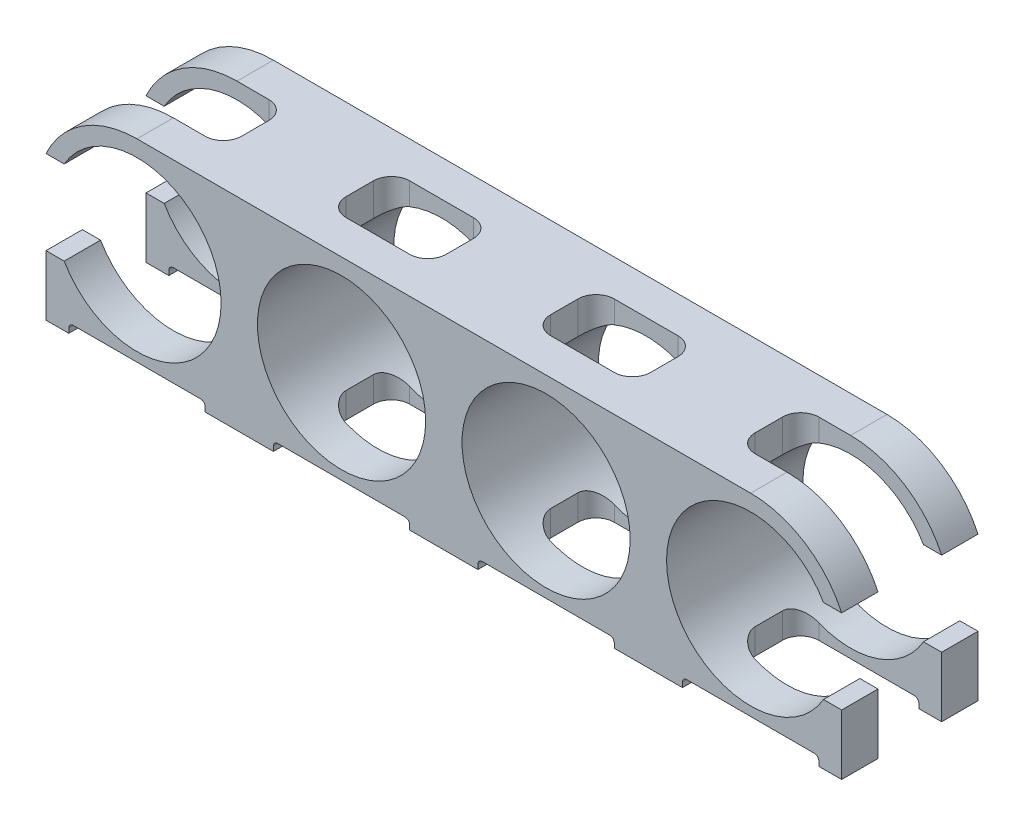
SolidWorks part; units mm, degrees
ref_plane "Front Plane" through (0, 0, 0) normal (0, 0, 1) x (1, 0, 0)
ref_plane "Top Plane" through (0, 0, 0) normal (0, 1, 0) x (1, 0, 0)
ref_plane "Right Plane" through (0, 0, 0) normal (1, 0, 0) x (0, 0, -1)
sketch "Sketch1" plane through (0, 0, 0) normal (0, 0, 1) x (1, 0, 0)
  line L0 (-41.7607, -4.625) -> (-43.7607, -4.625)
  line L1 (-41.7607, 4.625) -> (-43.7607, 4.625)
  line L2 (-33.75, 11.0275) -> (33.75, 11.0275)
  line L3 (-43.7607, -11.25) -> (43.7607, -11.25)
  line L4 (41.7607, 4.625) -> (43.7607, 4.625)
  line L5 (41.7607, -4.625) -> (43.7607, -4.625)
  line L7 (-43.7607, -11.25) -> (-43.7607, -4.625)
  line L8 (43.7607, -4.625) -> (43.7607, -11.25)
  circle A0 centre (-11.25, 0) radius 9.25 construction
  circle A1 centre (11.25, 0) radius 9.25 construction
  circle A2 centre (-33.75, 0) radius 9.25 construction
  circle A3 centre (33.75, 0) radius 9.25 construction
  arc A4 (-41.7607, 4.625) -> (-33.75, 9.25) centre (-33.75, 0) cw
  arc A5 (-43.7607, 4.625) -> (-33.75, 11.0275) centre (-33.75, 0) cw
  arc A6 (-33.75, 9.25) -> (-33.75, -9.25) centre (-33.75, 0) cw
  arc A7 (-33.75, -9.25) -> (-41.7607, -4.625) centre (-33.75, 0) cw
  circle A9 centre (-11.25, 0) radius 9.25
  circle A10 centre (11.25, 0) radius 9.25
  arc A12 (33.75, 11.0275) -> (43.7607, 4.625) centre (33.75, 0) cw
  arc A14 (33.75, 9.25) -> (41.7607, 4.625) centre (33.75, 0) cw
  arc A15 (41.7607, -4.625) -> (33.75, -9.25) centre (33.75, 0) cw
  arc A16 (33.75, 9.25) -> (33.75, -9.25) centre (33.75, 0) ccw
  point P30 (-43.7607, -7.9375)
  dimension "D5" = 18.5
  dimension "D6" = 60
  dimension "D8" = 2
  dimension "D1" = 22.5
  dimension "D2" = 11.25
  dimension "D3" = 22.5
  dimension "D4" = 22.5
  dimension "D7" = 2
extrude "Boss-Extrude1" add sketch "Sketch1" along normal blind 15
sketch "Sketch2" plane through (0, 11.0275, 0) normal (0, 1, 0) x (1, 0, 0)
  line L0 (0, 0) -> (0, -15) construction
  line L17 (30.25, -4) -> (46.25, -4)
  line L18 (-30.25, -9) -> (-46.25, -6) construction
  line L23 (-30.25, -6) -> (-46.25, -9) construction
  line L24 (-7.75, -9) -> (-14.75, -6) construction
  line L25 (33.75, -15) -> (-33.75, -15) construction
  line L27 (-7.75, -6) -> (-14.75, -9) construction
  line L33 (-48.25, -6) -> (-48.25, -9)
  line L34 (-30.25, -11) -> (-46.25, -11)
  line L35 (7.75, -4) -> (14.75, -4)
  line L36 (5.75, -6) -> (5.75, -9)
  line L37 (7.75, -11) -> (14.75, -11)
  line L38 (16.75, -6) -> (16.75, -9)
  line L39 (7.75, -6) -> (14.75, -9) construction
  line L40 (7.75, -9) -> (14.75, -6) construction
  line L41 (-28.25, -6) -> (-28.25, -9)
  line L42 (28.25, -6) -> (28.25, -9)
  line L43 (30.25, -11) -> (46.25, -11)
  line L44 (48.25, -6) -> (48.25, -9)
  line L45 (30.25, -6) -> (46.25, -9) construction
  line L46 (30.25, -9) -> (46.25, -6) construction
  line L47 (-16.75, -6) -> (-16.75, -9)
  line L48 (-7.75, -11) -> (-14.75, -11)
  line L49 (-5.75, -6) -> (-5.75, -9)
  line L50 (-7.75, -4) -> (-14.75, -4)
  line L51 (-30.25, -4) -> (-46.25, -4)
  arc A4 (16.75, -6) -> (14.75, -4) centre (14.75, -6) ccw
  arc A5 (7.75, -4) -> (5.75, -6) centre (7.75, -6) ccw
  arc A6 (5.75, -9) -> (7.75, -11) centre (7.75, -9) ccw
  arc A7 (14.75, -11) -> (16.75, -9) centre (14.75, -9) ccw
  arc A8 (48.25, -6) -> (46.25, -4) centre (46.25, -6) ccw
  arc A9 (30.25, -4) -> (28.25, -6) centre (30.25, -6) ccw
  arc A10 (28.25, -9) -> (30.25, -11) centre (30.25, -9) ccw
  arc A11 (46.25, -11) -> (48.25, -9) centre (46.25, -9) ccw
  arc A12 (-46.25, -11) -> (-48.25, -9) centre (-46.25, -9) cw
  arc A13 (-28.25, -9) -> (-30.25, -11) centre (-30.25, -9) cw
  arc A14 (-30.25, -4) -> (-28.25, -6) centre (-30.25, -6) cw
  arc A15 (-48.25, -6) -> (-46.25, -4) centre (-46.25, -6) cw
  arc A16 (-14.75, -11) -> (-16.75, -9) centre (-14.75, -9) cw
  arc A17 (-5.75, -9) -> (-7.75, -11) centre (-7.75, -9) cw
  arc A18 (-7.75, -4) -> (-5.75, -6) centre (-7.75, -6) cw
  arc A19 (-16.75, -6) -> (-14.75, -4) centre (-14.75, -6) cw
  point P0 (11.25, -7.5)
  point P6 (38.25, -7.5)
  point P20 (0, -7.5)
  dimension "D10" = 2
  dimension "D17" = 2
  dimension "D12" = 7
  dimension "D13" = 11
  dimension "D14" = 11.25
  dimension "D19" = 20
  dimension "D20" = 11.5
  dimension "D21" = 7
  dimension "D8" = 90
  dimension "D9" = 90
  dimension "D11" = 90
  dimension "D15" = 90
  dimension "D16" = 90
  dimension "D18" = 90
extrude "Cut-Extrude1" cut sketch "Sketch2" against normal up to surface (22.2775 mm away) up to face at (0, -11.25, 7.5)
sketch "Sketch3" plane through (0, -11.25, 0) normal (0, -1, 0) x (1, 0, 0)
  line L0 (0, 15) -> (0, 0) construction
  line L1 (-43.7607, 15) -> (43.7607, 15) construction
  line L2 (-43.7607, 0) -> (43.7607, 0) construction
  line L3 (-28.25, 7.5) -> (-16.75, 7.5) construction
  line L4 (-28.25, 6) -> (-28.25, 9) construction
  line L5 (-16.75, 9) -> (-16.75, 6) construction
  line L6 (16.75, 7.5) -> (28.25, 7.5) construction
  line L7 (16.75, 6) -> (16.75, 9) construction
  line L8 (28.25, 9) -> (28.25, 6) construction
  circle A0 centre (0, 7.5) radius 1.325
  circle A1 centre (-22.5, 7.5) radius 1.325
  circle A2 centre (22.5, 7.5) radius 1.325
  point P13 (0, 7.5)
  point P20 (-22.5, 7.5)
  point P21 (22.5, 7.5)
  dimension "D1" = 2.65
extrude "Cut-Extrude2" cut sketch "Sketch3" against normal blind 7
thread "Thread1" pitch 0.5 method cut profile "Thread Profile1" start angle 0, offset 0, length 0, pitch 0.5, diameter 2.65
ref_plane "Plane1" through (-21.175, -11.25, 7.5) normal (0, 0, 1) x (1, 0, 0)
sketch "Thread Profile1" plane through (-21.175, -11.25, 7.5) normal (0, 0, 1) x (1, 0, 0)
  line L0 (0, 0) -> (0, 0.5) construction
  line L1 (0, 0) -> (0.2706, 0.1562)
  line L2 (0.2706, 0.1562) -> (0.2706, 0.2187)
  line L3 (0.2706, 0.2187) -> (0, 0.375)
  line L4 (0.2706, 0.1875) -> (0, 0.1875) construction
  line L11 (0, 0) -> (0, 0.375)
  point P2 (0, 0)
  dimension "Pitch" = 0.5
  dimension "Profile_Angle" = 60
  dimension "Profile_Land" = 0.0625
  dimension "Profile_Height" = 0.2706
thread "Thread2" pitch 0.5 method cut profile "Thread Profile2" start angle 0, offset 0, length 0, pitch 0.5, diameter 2.65
ref_plane "Plane2" through (1.325, -11.25, 7.5) normal (0, 0, 1) x (1, 0, 0)
sketch "Thread Profile2" plane through (1.325, -11.25, 7.5) normal (0, 0, 1) x (1, 0, 0)
  line L0 (0, 0) -> (0, 0.5) construction
  line L1 (0, 0) -> (0.2706, 0.1562)
  line L2 (0.2706, 0.1562) -> (0.2706, 0.2187)
  line L3 (0.2706, 0.2187) -> (0, 0.375)
  line L4 (0.2706, 0.1875) -> (0, 0.1875) construction
  line L11 (0, 0) -> (0, 0.375)
  point P2 (0, 0)
  dimension "Pitch" = 0.5
  dimension "Profile_Angle" = 60
  dimension "Profile_Land" = 0.0625
  dimension "Profile_Height" = 0.2706
thread "Thread3" pitch 0.5 method cut profile "Thread Profile3" start angle 0, offset 0, length 0, pitch 0.5, diameter 2.65
ref_plane "Plane3" through (23.825, -11.25, 7.5) normal (0, 0, 1) x (1, 0, 0)
sketch "Thread Profile3" plane through (23.825, -11.25, 7.5) normal (0, 0, 1) x (1, 0, 0)
  line L0 (0, 0) -> (0, 0.5) construction
  line L1 (0, 0) -> (0.2706, 0.1562)
  line L2 (0.2706, 0.1562) -> (0.2706, 0.2187)
  line L3 (0.2706, 0.2187) -> (0, 0.375)
  line L4 (0.2706, 0.1875) -> (0, 0.1875) construction
  line L11 (0, 0) -> (0, 0.375)
  point P2 (0, 0)
  dimension "Pitch" = 0.5
  dimension "Profile_Angle" = 60
  dimension "Profile_Land" = 0.0625
  dimension "Profile_Height" = 0.2706
sketch "Sketch4" plane through (0, 0, 15) normal (0, 0, 1) x (1, 0, 0)
  line L0 (-20.5, 0) -> (-2, 0) construction
  line L1 (-43.7607, -11.25) -> (43.7607, -11.25) construction
  line L2 (-18.25, -10.25) -> (-4.25, -10.25)
  line L3 (-18.75, -10.75) -> (-18.75, -11.25)
  line L4 (-18.75, -11.25) -> (-3.75, -11.25)
  line L5 (-3.75, -10.75) -> (-3.75, -11.25)
  line L6 (-18.75, -10.25) -> (-3.75, -11.25) construction
  line L7 (-18.75, -11.25) -> (-3.75, -10.25) construction
  line L8 (0, 11.0275) -> (0, -11.25) construction
  line L9 (33.75, 11.0275) -> (-33.75, 11.0275) construction
  line L10 (-20.5, 0) -> (-24.5, 0) construction
  line L11 (-22.5, 11.0275) -> (-22.5, 0) construction
  line L12 (-26.25, -11.25) -> (-41.25, -10.25) construction
  line L13 (-26.25, -10.25) -> (-41.25, -11.25) construction
  line L14 (-41.25, -10.75) -> (-41.25, -11.25)
  line L15 (-26.25, -11.25) -> (-41.25, -11.25)
  line L16 (-26.25, -10.75) -> (-26.25, -11.25)
  line L17 (-26.75, -10.25) -> (-40.75, -10.25)
  line L18 (26.25, -10.25) -> (41.25, -11.25) construction
  line L19 (26.25, -11.25) -> (41.25, -10.25) construction
  line L20 (18.75, -11.25) -> (3.75, -10.25) construction
  line L21 (18.75, -10.25) -> (3.75, -11.25) construction
  line L22 (26.75, -10.25) -> (40.75, -10.25)
  line L23 (26.25, -10.75) -> (26.25, -11.25)
  line L24 (26.25, -11.25) -> (41.25, -11.25)
  line L25 (41.25, -10.75) -> (41.25, -11.25)
  line L26 (3.75, -10.75) -> (3.75, -11.25)
  line L27 (18.75, -11.25) -> (3.75, -11.25)
  line L28 (18.75, -10.75) -> (18.75, -11.25)
  line L29 (18.25, -10.25) -> (4.25, -10.25)
  circle A0 centre (-11.25, 0) radius 9.25 construction
  arc A1 (-4.25, -10.25) -> (-3.75, -10.75) centre (-4.25, -10.75) cw
  arc A2 (-18.25, -10.25) -> (-18.75, -10.75) centre (-18.25, -10.75) ccw
  arc A3 (-41.7607, -4.625) -> (-41.7607, 4.625) centre (-33.75, 0) ccw construction
  arc A4 (-26.75, -10.25) -> (-26.25, -10.75) centre (-26.75, -10.75) cw
  arc A5 (-40.75, -10.25) -> (-41.25, -10.75) centre (-40.75, -10.75) ccw
  arc A6 (40.75, -10.25) -> (41.25, -10.75) centre (40.75, -10.75) cw
  arc A7 (26.75, -10.25) -> (26.25, -10.75) centre (26.75, -10.75) ccw
  arc A8 (18.25, -10.25) -> (18.75, -10.75) centre (18.25, -10.75) cw
  arc A9 (4.25, -10.25) -> (3.75, -10.75) centre (4.25, -10.75) ccw
  point P5 (-11.25, -10.75)
  point P13 (-11.25, 0)
  point P39 (-33.75, -10.75)
  point P60 (33.75, -10.75)
  point P61 (11.25, -10.75)
  dimension "D3" = 0.5
  dimension "D1" = 1
  dimension "D2" = 15
extrude "Cut-Extrude3" cut sketch "Sketch4" against normal up to surface (15 mm away) up to face at (20.5, 0, 0)
